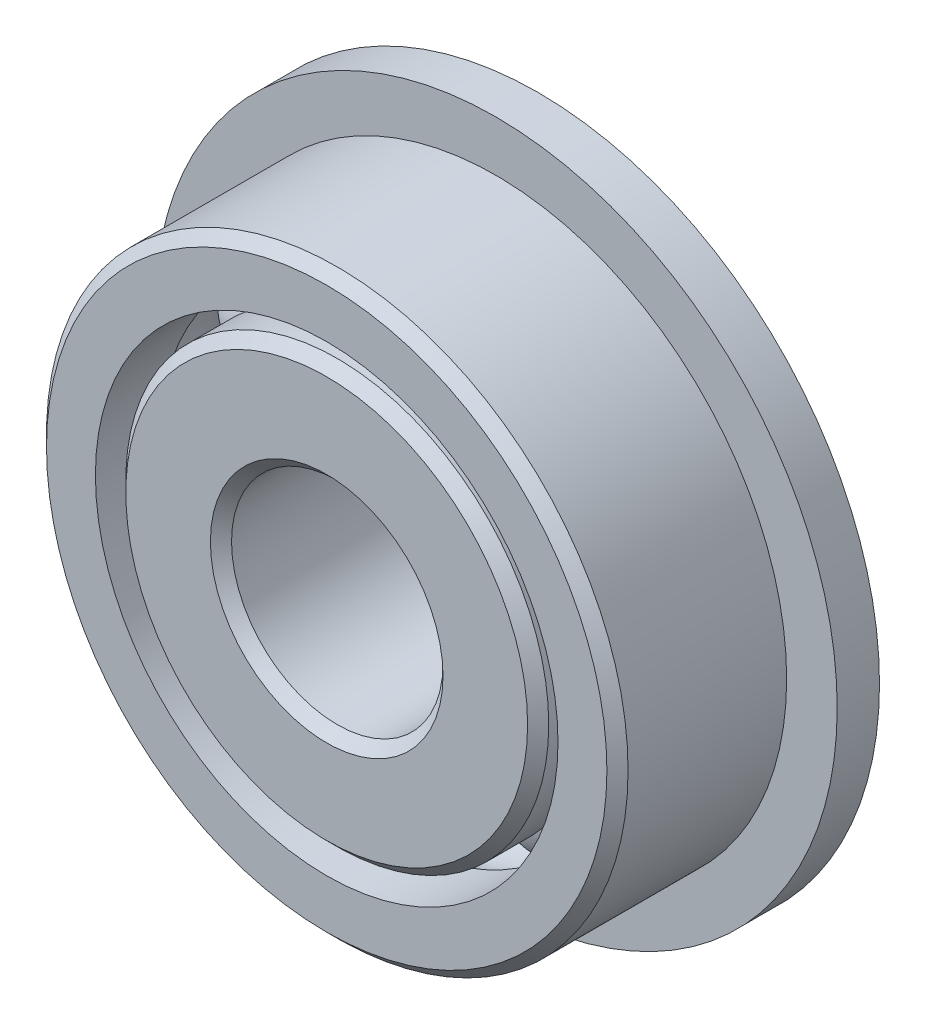
SolidWorks part; units mm, degrees
ref_plane "Front Plane" through (0, 0, 0) normal (0, 0, 1) x (1, 0, 0)
ref_plane "Top Plane" through (0, 0, 0) normal (0, 1, 0) x (1, 0, 0)
ref_plane "Right Plane" through (0, 0, 0) normal (1, 0, 0) x (0, 0, -1)
sketch "Sketch1" plane through (0, 0, 0) normal (1, 0, 0) x (0, 0, -1)
  line L0 (-3.175, 0) -> (3.175, 0) construction
  line L1 (0, 8.7312) -> (0, -8.7312) construction
  line L2 (2.8575, 8.7312) -> (-2.8575, 8.7312)
  line L3 (-2.8575, 8.7312) -> (-3.175, 8.4138)
  line L4 (-3.175, 8.4138) -> (-3.175, 6.9453)
  line L5 (-3.175, 6.9453) -> (-1.2392, 6.9453)
  line L6 (3.175, 6.9453) -> (1.2392, 6.9453)
  line L7 (3.175, 8.4138) -> (3.175, 6.9453)
  line L8 (2.8575, 8.7312) -> (3.175, 8.4138)
  line L9 (0, 8.7312) -> (0, 5.9531) construction
  line L10 (0, 5.9531) -> (0, 3.175) construction
  line L11 (3.175, 6.35) -> (3.175, -6.35) construction
  line L12 (-3.175, 3.175) -> (3.175, 3.175) construction
  line L13 (0, 4.3656) -> (0, 3.175) construction
  line L14 (0, 7.5406) -> (0, 8.7312) construction
  line L15 (3.175, 6.35) -> (0, 6.35) construction
  circle A1 centre (0, 5.9531) radius 1.5875 construction
  arc A2 (-1.2392, 6.9453) -> (1.2392, 6.9453) centre (0, 5.9531) cw
  point P14 (0, 3.175)
  point P22 (0, 4.3656)
  point P23 (0, 7.5406)
  dimension "D3" = 3.175
  dimension "D6" = 0.5953
  dimension "D1" = 45
  dimension "Width" = 6.35
  dimension "OD" = 17.4625
  dimension "D2" = 0.3175
  dimension "Shaft Dia" = 6.35
  dimension "D4" = 12.7
  dimension "D5" = 1.1906
revolve "Revolve1" add sketch "Sketch1" angle 360 about L0
sketch "Sketch3" plane through (0, 0, 0) normal (1, 0, 0) x (0, 0, -1)
  line L1 (-3.175, 8.4138) -> (-3.175, 6.9453) construction
  line L2 (-2.8575, 8.7312) -> (-3.175, 8.4138) construction
  line L3 (-3.175, 4.9609) -> (-3.175, 3.4925) construction
  line L4 (-3.175, 3.4925) -> (-3.175, 6.0325)
  line L5 (-3.175, 3.4925) -> (-2.8575, 3.175)
  line L6 (-2.8575, 3.175) -> (4.4577, 3.175)
  line L7 (-3.175, 8.4138) -> (-3.175, -8.4138) construction
  line L8 (4.4577, 3.175) -> (4.7752, 3.4925)
  line L9 (0, 0) -> (4.7752, 0) construction
  line L13 (2.8575, 8.7312) -> (3.175, 8.4138) construction
  line L14 (-3.175, 6.0325) -> (-2.8575, 6.35)
  line L15 (-2.8575, 6.35) -> (-1.5371, 6.35)
  line L16 (1.5371, 6.35) -> (4.4577, 6.35)
  line L17 (4.4577, 6.35) -> (4.7752, 6.0325)
  line L18 (4.7752, 6.0325) -> (4.7752, 3.4925)
  circle A0 centre (0, 5.9531) radius 1.5875 construction
  arc A1 (-1.5371, 6.35) -> (1.5371, 6.35) centre (0, 5.9531) ccw
  dimension "D1" = 45
  dimension "Ring Wd" = 7.9502
  dimension "Inner Ring OD" = 12.7
revolve "Revolve3" add sketch "Sketch3" angle 360 about L0
sketch "Sketch6" plane through (0, 0, 0) normal (1, 0, 0) x (0, 0, -1)
  line L1 (3.175, 6.9453) -> (1.905, 6.9453)
  line L2 (3.175, 6.9453) -> (3.175, 10.2489)
  line L3 (3.175, 10.2489) -> (1.905, 10.2489)
  line L4 (1.905, 6.9453) -> (1.905, 10.2489)
  line L5 (3.175, 0) -> (-3.175, 0) construction
  dimension "Flange OD" = 20.4978
  dimension "Flange Thickness" = 1.27
revolve "Revolve6" add sketch "Sketch6" angle 360 about L5
sketch "Sketch4" plane through (0, 0, 0) normal (1, 0, 0) x (0, 0, -1)
  line L0 (-1.5875, 5.9531) -> (1.5875, 5.9531)
  circle A0 centre (0, 5.9531) radius 1.5875 construction
  arc A1 (1.5875, 5.9531) -> (-1.5875, 5.9531) centre (0, 5.9531) ccw
revolve "Revolve4" add sketch "Sketch4" angle 360 about L0
ref_axis "Axis1" through (0, 0, -3.175) along (0, 0, 1)
pattern_circular "CirPattern1" count 8 every 45 about axis through (0, 0, -3.175) along (0, 0, 1) of bodies 104
sketch "Sketch5" plane through (0, 0, 0) normal (1, 0, 0) x (0, 0, -1)
  line L0 (-3.175, 6.9453) -> (-1.2392, 6.9453) construction
  line L1 (-3.0162, 6.9453) -> (-1.5371, 6.9453)
  line L2 (-3.0162, 6.9453) -> (-3.0162, 6.35)
  line L3 (-3.0162, 6.35) -> (-1.5371, 6.35)
  line L4 (-1.5371, 6.9453) -> (-1.5371, 6.35)
  line L6 (3.175, 6.9453) -> (1.2392, 6.9453) construction
  line L7 (3.0163, 6.9453) -> (1.5371, 6.9453)
  line L8 (3.0163, 6.9453) -> (3.0163, 6.35)
  line L9 (3.0163, 6.35) -> (1.5371, 6.35)
  line L10 (1.5371, 6.9453) -> (1.5371, 6.35)
  line L12 (-2.8575, 8.7312) -> (-3.175, 8.4138) construction
  line L13 (3.175, 6.35) -> (0, 6.35) construction
  line L15 (-2.8575, 6.35) -> (-1.5371, 6.35) construction
  line L16 (3.0163, 6.9453) -> (3.0163, 8.5725) construction
  line L17 (2.8575, 8.7312) -> (3.175, 8.4138) construction
  point P18 (-3.0162, 8.5725)
revolve "Revolve5" [suppressed] add sketch "Sketch5" angle 360 about L0
equation "\"D2@Sketch1\" = \"Width@Sketch1\"*.05"
equation "\"D2@CirPattern1\" = 360/\"Balls@CirPattern1\""
equation "\"D4@Sketch1\"=\"Inner Ring OD@Sketch3\""
equation "\"D3@Sketch1\"=\"Width@Sketch1\"/2"
equation "\"D6@Sketch1\"=\"D5@Sketch1\"/2"
